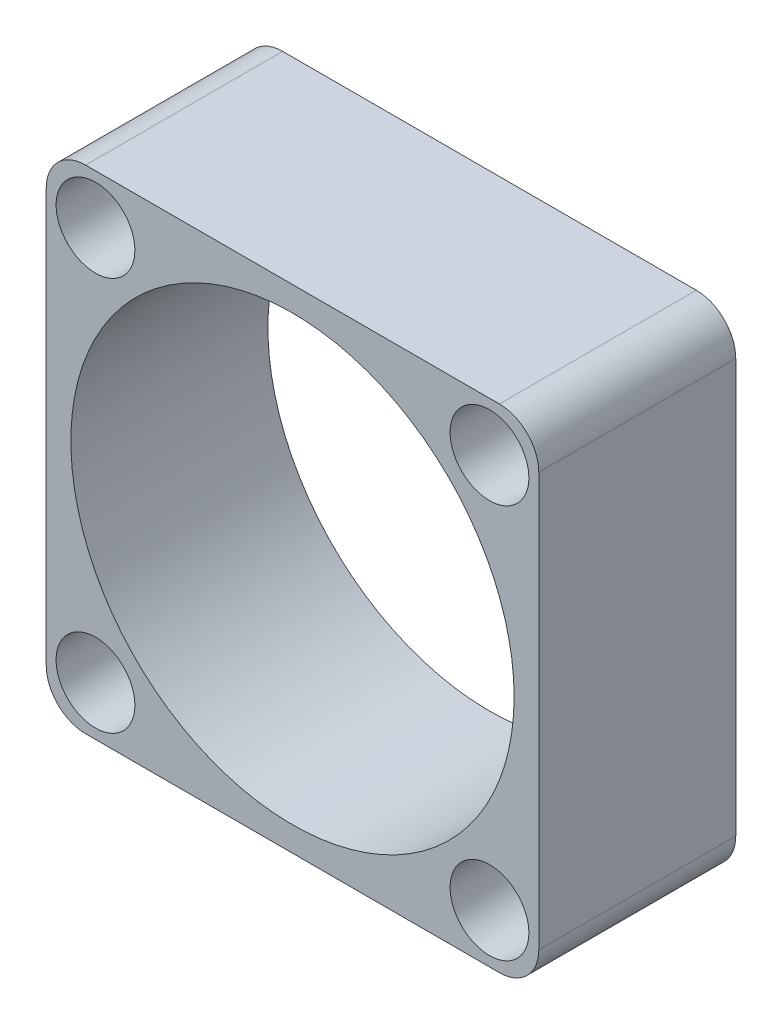
SolidWorks part; units mm, degrees
material "ABS PC"
ref_plane "Front Plane" through (0, 0, 0) normal (0, 0, 1) x (1, 0, 0)
ref_plane "Top Plane" through (0, 0, 0) normal (0, 1, 0) x (1, 0, 0)
ref_plane "Right Plane" through (0, 0, 0) normal (1, 0, 0) x (0, 0, -1)
sketch "Sketch1" plane through (0, 0, 0) normal (0, 0, 1) x (1, 0, 0)
  line L1 (0, 0) -> (25, 0)
  line L2 (0, 0) -> (0, 25)
  line L3 (0, 25) -> (25, 25)
  line L4 (25, 0) -> (25, 25)
  dimension "D1" = 25
  dimension "D2" = 25
extrude "Boss-Extrude1" add sketch "Sketch1" along normal blind 10
sketch "Sketch3" plane through (0, 0, 10) normal (0, 0, 1) x (1, 0, 0)
  line L0 (0, 12.5) -> (12.5, 12.5) construction
  line L1 (0, 25) -> (0, 0) construction
  line L2 (12.5, 12.5) -> (12.5, 0) construction
  line L3 (0, 0) -> (25, 0) construction
  circle A0 centre (12.5, 12.5) radius 11.25
  circle A1 centre (2.5, 22.5) radius 2
  circle A2 centre (22.5, 22.5) radius 2
  circle A3 centre (22.5, 2.5) radius 2
  circle A4 centre (2.5, 2.5) radius 2
  dimension "D1" = 22.5
  dimension "D6" = 4
  dimension "D2" = 20
  dimension "D3" = 20
  dimension "D4" = 20
  dimension "D5" = 20
extrude "Cut-Extrude1" cut sketch "Sketch3" against normal blind 10 contours A0 | A1 | A4 | A3 | A2 region at (12.5, 12.5, 10) region at (2.5, 22.5, 10) region at (22.5, 22.5, 10) region at (22.5, 2.5, 10) region at (2.5, 2.5, 10)
fillet "Fillet1" radius 2 4 edges at (0, 0, 5) (25, 0, 5) (0, 25, 5) (25, 25, 5)
